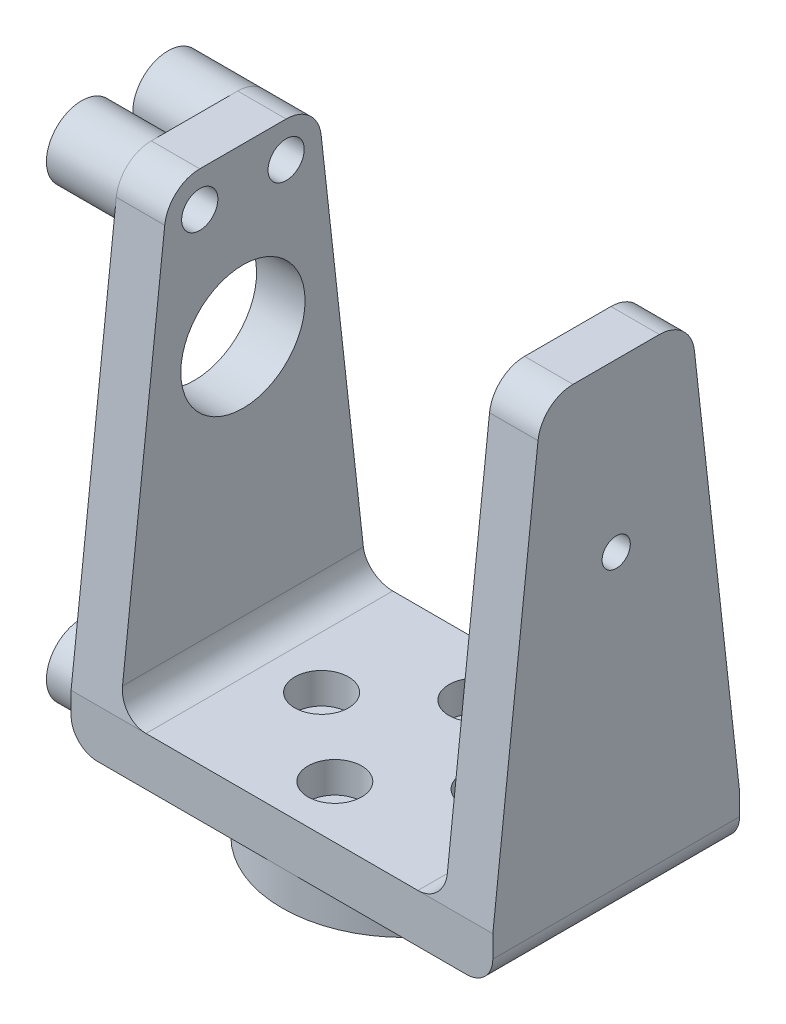
SolidWorks part; units mm, degrees
ref_plane "Front Plane" through (0, 0, 0) normal (0, 0, 1) x (1, 0, 0)
ref_plane "Top Plane" through (0, 0, 0) normal (0, 1, 0) x (1, 0, 0)
ref_plane "Right Plane" through (0, 0, 0) normal (1, 0, 0) x (0, 0, -1)
sketch "Sketch6" plane through (0, 0, 0) normal (0, 0, 1) x (1, 0, 0)
  line L0 (0, 0) -> (-14, 0)
  line L2 (-23.9289, 9.9289) -> (-23.9289, 60)
  line L3 (-23.9289, 60) -> (-18.4289, 60)
  line L4 (-18.4289, 60) -> (-18.4289, 12)
  line L6 (-11.9289, 5.5) -> (0, 5.5)
  line L7 (0, 5.5) -> (0, 0)
  line L8 (-14, 0) -> (-23.9289, 0)
  line L9 (-23.9289, 0) -> (-23.9289, 9.9289)
  line L10 (-18.4289, 12) -> (-18.4289, 5.5)
  line L11 (-18.4289, 5.5) -> (-11.9289, 5.5)
  dimension "D1" = 5.5
  dimension "D2" = 60
  dimension "D3" = 14
  dimension "D4" = 23.9289
  dimension "D5" = 48
  dimension "D6" = 50.0711
  dimension "D7" = 11.9289
extrude "Gimbal Mount Body" add sketch "Sketch6" against normal blind 28
mirror "Gimbal Mount Body Mirror" about plane through (0, 0, 0) normal (1, 0, 0) of "Gimbal Mount Body"
sketch "Sketch7" plane through (-23.9289, 0, 0) normal (-1, 0, 0) x (0, 0, 1)
  line L2 (-14, 12) -> (-14, 60) construction
  line L3 (-28, 60) -> (0, 60) construction
  circle A0 centre (-14, 36) radius 7.05
  dimension "D1" = 14.1
  dimension "D2" = 48
extrude "Servo Gear Mound Cut Out" cut sketch "Sketch7" against normal up to surface (5.5 mm away) up to face at (-18.4289, 32.75, -14)
sketch "Servo Mounting Pattern Reference Sketch2" plane through (-23.9289, 0, 0) normal (-1, 0, 0) x (0, 0, 1)
  line L0 (-14, 36) -> (-14, 50.94) construction
  line L1 (-14, 36) -> (-14, 0.06) construction
  line L2 (-18.9, 50.94) -> (-9.1, 50.94) construction
  line L3 (-18.9, 0.06) -> (-9.1, 0.06) construction
  circle A0 centre (-18.9, 50.94) radius 2.15 construction
  circle A1 centre (-9.1, 50.94) radius 2.15 construction
  circle A2 centre (-18.9, 0.06) radius 2.15 construction
  circle A3 centre (-9.1, 0.06) radius 2.15 construction
  point P9 (-14, 0.06)
  point P11 (-14, 50.94)
  dimension "D5" = 4.3
  dimension "D1" = 9.8
  dimension "D2" = 9.8
  dimension "D3" = 14.94
  dimension "D4" = 35.94
sketch "Sketch14" plane through (-23.9289, 0, 0) normal (-1, 0, 0) x (0, 0, 1)
  line L17 (-18.9, -3.94) -> (-9.1, -3.94)
  line L20 (-28, 0) -> (0, 0) construction
  line L21 (-22.8995, 0) -> (-5.1005, 0)
  arc A6 (-22.8995, 0) -> (-18.9, -3.94) centre (-18.9, 0.06) ccw
  arc A7 (-9.1, -3.94) -> (-5.1005, 0) centre (-9.1, 0.06) ccw
  dimension "D1" = 4
extrude "Boss-Extrude6" add sketch "Sketch14" against normal up to surface (5.5 mm away) up to face at (-18.4289, 43.05, -14)
sketch "Sketch15" plane through (-23.9289, 0, 0) normal (-1, 0, 0) x (0, 0, 1)
  circle A0 centre (-18.9, 50.94) radius 4
  circle A1 centre (-9.1, 50.94) radius 4
  circle A2 centre (-18.9, 0.06) radius 4
  circle A3 centre (-9.1, 0.06) radius 4
  dimension "D1" = 8
extrude "Boss-Extrude7" add sketch "Sketch15" along normal blind 7.9
sketch "Sketch17" plane through (23.9289, 0, 0) normal (1, 0, 0) x (0, 0, -1)
  circle A0 centre (14, 36) radius 1.6
  circle A1 centre (14, 36) radius 7.05 construction
  circle A2 centre (14, 36) radius 7.05 construction
  dimension "D1" = 3.2
extrude "Cut-Extrude2" cut sketch "Sketch17" against normal up to surface (5.5 mm away) up to face at (18.4289, 32.75, -14)
sketch "Sketch19" plane through (0, 0, 0) normal (0, -1, 0) x (1, 0, 0)
  line L6 (0, 0) -> (0, -28) construction
  line L7 (-23.9289, -28) -> (23.9289, -28) construction
  line L8 (-23.9289, 0) -> (23.9289, 0) construction
  circle A0 centre (0, -14) radius 14
extrude "Boss-Extrude9" add sketch "Sketch19" along normal up to surface (3.94 mm away) up to face at (-21.1789, -3.94, -14)
sketch "Sketch20" plane through (0, -3.94, 0) normal (0, -1, 0) x (1, 0, 0)
  line L0 (-9.5, -14) -> (9.5, -14) construction
  line L1 (0, -6) -> (0, -22) construction
  circle A0 centre (0, -6) radius 1.75
  circle A1 centre (-9.5, -14) radius 1.75
  circle A2 centre (9.5, -14) radius 1.75
  circle A3 centre (0, -22) radius 1.75
  point P0 (0, -14)
  point P5 (0, -14)
  point P7 (0, -14)
  dimension "D3" = 3.5
  dimension "D1" = 16
  dimension "D2" = 19
extrude "Cut-Extrude4" cut sketch "Sketch20" against normal up to surface (9.44 mm away) up to face at (0, 5.5, -14)
sketch "Sketch21" plane through (-31.8289, 0, 0) normal (-1, 0, 0) x (0, 0, 1)
  circle A0 centre (-18.9, 50.94) radius 2.055
  circle A1 centre (-9.1, 50.94) radius 2.055
  circle A2 centre (-9.1, 0.06) radius 2.055
  circle A3 centre (-18.9, 0.06) radius 2.055
  dimension "D1" = 4.11
extrude "Cut-Extrude5" cut sketch "Sketch21" against normal up to surface (13.4 mm away) up to face at (-18.4289, 43.05, -14)
sketch "Sketch30" plane through (18.4289, 0, 0) normal (-1, 0, 0) x (0, 0, 1)
  circle A0 centre (-14, 36) radius 1.6
  circle A1 centre (-14, 36) radius 1.6 construction
  circle A2 centre (-14, 36) radius 2.3
  dimension "D1" = 4.6
extrude "Boss-Extrude10" add sketch "Sketch30" along normal blind 0.5
sketch "Sketch22" plane through (23.9289, 0, 0) normal (1, 0, 0) x (0, 0, -1)
  circle A0 centre (14, 36) radius 3.75
  dimension "D1" = 7.5
extrude "Cut-Extrude6" [suppressed] cut sketch "Sketch22" against normal blind 1
sketch "Sketch24" [suppressed] plane through (18.4289, 0, 0) normal (-1, 0, 0) x (0, 0, 1)
  circle A0 centre (-14, 36) radius 3.75 construction
  circle A1 centre (-14, 36) radius 3.75
extrude "Cut-Extrude8" [suppressed] cut sketch "Sketch24" against normal blind 3.1
sketch "Sketch25" [suppressed] plane through (22.9289, 0, 0) normal (1, 0, 0) x (0, 0, -1)
  circle A0 centre (14, 36) radius 3.25
  circle A2 centre (14, 36) radius 3.75 construction
  circle A3 centre (14, 36) radius 3.75
  circle M4 centre (14, 36) radius 1.75
  dimension "D1" = 6.5
extrude "Cut-Extrude9" [suppressed] cut sketch "Sketch25" against normal blind 0.25 contours A0 M4
sketch "Sketch26" [suppressed] plane through (21.5289, 0, 0) normal (-1, 0, 0) x (0, 0, 1)
  circle A0 centre (-14, 36) radius 3.25
  circle A2 centre (-14, 36) radius 3.75 construction
  circle A3 centre (-14, 36) radius 3.75
  circle M5 centre (-14, 36) radius 1.75
  dimension "D1" = 6.5
extrude "Cut-Extrude10" [suppressed] cut sketch "Sketch26" against normal blind 0.25 contours A0 M5
sketch "Sketch28" plane through (-23.9289, 0, 0) normal (-1, 0, 0) x (0, 0, 1)
  line L0 (-28, 5.5) -> (0, 5.5) construction
  line L1 (-28, 5.5) -> (0, 5.5) construction
  line L2 (0, 5.5) -> (-6.087, 60)
  line L3 (-28, 60) -> (0, 60) construction
  line L4 (-28, 5.5) -> (-21.913, 60)
  line L5 (-6.087, 60) -> (0, 60)
  line L6 (0, 60) -> (0, 5.5)
  line L7 (-21.913, 60) -> (-28, 60)
  line L8 (-28, 60) -> (-28, 5.5)
  circle A0 centre (-9.1, 50.94) radius 4 construction
  circle A1 centre (-18.9, 50.94) radius 4 construction
extrude "Cut-Extrude11" cut sketch "Sketch28" against normal through all
sketch "Sketch29" plane through (0, 5.5, 0) normal (0, 1, 0) x (1, 0, 0)
  circle A0 centre (0, 22) radius 3.05
  circle A1 centre (-9.5, 14) radius 3.05
  circle A2 centre (0, 6) radius 3.05
  circle A3 centre (9.5, 14) radius 3.05
  dimension "D1" = 6.1
extrude "Cut-Extrude12" cut sketch "Sketch29" against normal blind 3.5
sketch "Sketch23" plane through (-23.9289, 0, 0) normal (-1, 0, 0) x (0, 0, 1)
  line L1 (-21.913, 60) -> (-6.087, 60)
  line L2 (-21.913, 60) -> (-22.4781, 54.94)
  line L3 (-22.4781, 54.94) -> (-5.5219, 54.94)
  line L4 (-6.087, 60) -> (-5.5219, 54.94)
  line L5 (-22.8753, 51.384) -> (-21.913, 60) construction
  line L6 (-6.087, 60) -> (-5.1247, 51.384) construction
  circle A0 centre (-9.1, 50.94) radius 4 construction
extrude "Cut-Extrude7" cut sketch "Sketch23" against normal through all
fillet "Fillet4" radius 3 5 edges at (-23.9289, 0, -2.5502) (-23.9289, 0, -25.4498) (23.9289, 0, -14) (-18.4289, 5.5, -14) (18.4289, 5.5, -14)
fillet "Fillet5" radius 4 4 edges at (21.1789, 54.94, -5.5219) (21.1789, 54.94, -22.4781) (-21.1789, 54.94, -22.4781) (-21.1789, 54.94, -5.5219)
